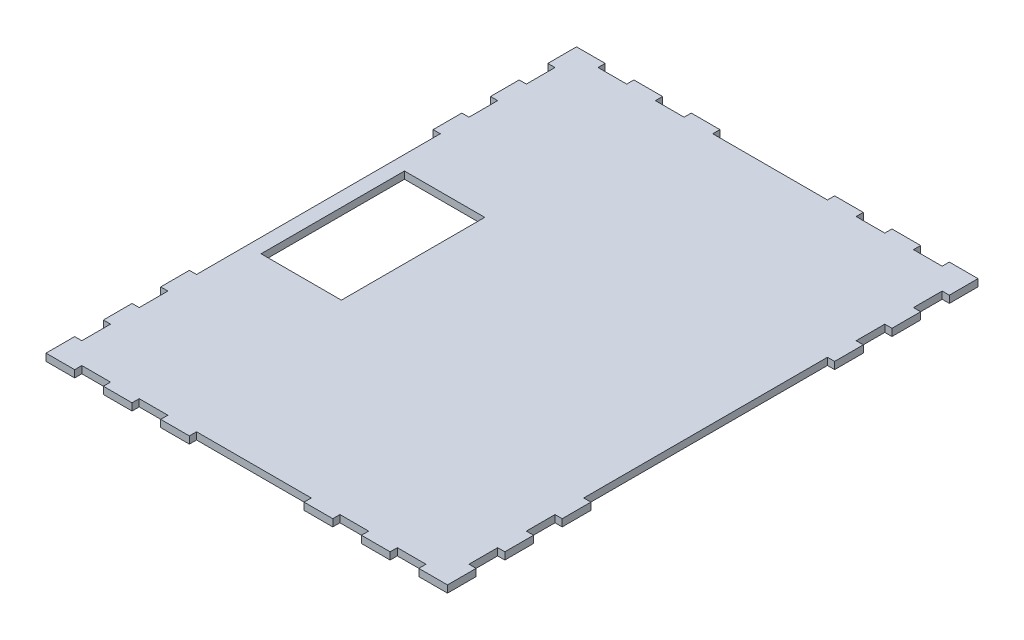
SolidWorks part; units mm, degrees
material "Acrylic (Medium-high impact)"
ref_plane "Front Plane" through (0, 0, 0) normal (0, 0, 1) x (1, 0, 0)
ref_plane "Top Plane" through (0, 0, 0) normal (0, 1, 0) x (1, 0, 0)
ref_plane "Right Plane" through (0, 0, 0) normal (1, 0, 0) x (0, 0, -1)
sketch "Sketch1" plane through (0, 0, 0) normal (0, 1, 0) x (1, 0, 0)
  line L0 (0, 209.55) -> (0, 196.85)
  line L1 (0, 0) -> (177.8, 0)
  line L2 (0, 0) -> (0, 234.95)
  line L3 (0, 234.95) -> (177.8, 234.95)
  line L4 (177.8, 0) -> (177.8, 234.95)
  line L5 (0, 234.95) -> (3.175, 234.95)
  line L6 (0, 234.95) -> (0, 0)
  line L7 (0, 0) -> (3.175, 0)
  line L8 (3.175, 234.95) -> (3.175, 0)
  line L9 (177.8, 234.95) -> (174.625, 234.95)
  line L10 (177.8, 234.95) -> (177.8, 0)
  line L11 (177.8, 0) -> (174.625, 0)
  line L12 (174.625, 234.95) -> (174.625, 0)
  line L13 (0, 234.95) -> (3.175, 234.95)
  line L14 (0, 234.95) -> (0, 222.25)
  line L15 (0, 222.25) -> (3.175, 222.25)
  line L16 (3.175, 234.95) -> (3.175, 222.25)
  line L17 (0, 209.55) -> (3.175, 209.55)
  line L18 (3.175, 209.55) -> (3.175, 196.85)
  line L19 (0, 196.85) -> (3.175, 196.85)
  line L20 (0, 184.15) -> (0, 171.45)
  line L21 (0, 184.15) -> (3.175, 184.15)
  line L22 (3.175, 184.15) -> (3.175, 171.45)
  line L23 (0, 171.45) -> (3.175, 171.45)
  line L24 (0, 117.475) -> (177.8, 117.475) construction
  line L25 (88.9, 234.95) -> (88.9, 0) construction
  line L26 (177.8, 171.45) -> (174.625, 171.45)
  line L27 (174.625, 184.15) -> (174.625, 171.45)
  line L28 (177.8, 184.15) -> (174.625, 184.15)
  line L29 (177.8, 184.15) -> (177.8, 171.45)
  line L30 (177.8, 196.85) -> (174.625, 196.85)
  line L31 (174.625, 209.55) -> (174.625, 196.85)
  line L32 (177.8, 209.55) -> (174.625, 209.55)
  line L33 (174.625, 234.95) -> (174.625, 222.25)
  line L34 (177.8, 222.25) -> (174.625, 222.25)
  line L35 (177.8, 234.95) -> (177.8, 222.25)
  line L36 (177.8, 234.95) -> (174.625, 234.95)
  line L37 (177.8, 234.95) -> (177.8, 0)
  line L38 (177.8, 234.95) -> (174.625, 234.95)
  line L39 (177.8, 209.55) -> (177.8, 196.85)
  line L40 (177.8, 25.4) -> (177.8, 38.1)
  line L41 (177.8, 0) -> (174.625, 0)
  line L42 (177.8, 0) -> (174.625, 0)
  line L43 (177.8, 0) -> (177.8, 12.7)
  line L44 (177.8, 12.7) -> (174.625, 12.7)
  line L45 (174.625, 0) -> (174.625, 12.7)
  line L46 (177.8, 25.4) -> (174.625, 25.4)
  line L47 (174.625, 25.4) -> (174.625, 38.1)
  line L48 (177.8, 38.1) -> (174.625, 38.1)
  line L49 (177.8, 50.8) -> (177.8, 63.5)
  line L50 (177.8, 50.8) -> (174.625, 50.8)
  line L51 (174.625, 50.8) -> (174.625, 63.5)
  line L52 (177.8, 63.5) -> (174.625, 63.5)
  line L53 (0, 63.5) -> (3.175, 63.5)
  line L54 (3.175, 50.8) -> (3.175, 63.5)
  line L55 (0, 50.8) -> (3.175, 50.8)
  line L56 (0, 50.8) -> (0, 63.5)
  line L57 (0, 38.1) -> (3.175, 38.1)
  line L58 (3.175, 25.4) -> (3.175, 38.1)
  line L59 (0, 25.4) -> (3.175, 25.4)
  line L60 (3.175, 0) -> (3.175, 12.7)
  line L61 (0, 12.7) -> (3.175, 12.7)
  line L62 (0, 0) -> (0, 12.7)
  line L63 (0, 0) -> (3.175, 0)
  line L64 (177.8, 0) -> (174.625, 0)
  line L65 (0, 0) -> (3.175, 0)
  line L66 (0, 0) -> (177.8, 0)
  line L67 (0, 25.4) -> (0, 38.1)
  dimension "D1" = 234.95
  dimension "D2" = 177.8
  dimension "D3" = 3.175
  dimension "D4" = 3.175
  dimension "D5" = 12.7
  dimension "D6" = 3.175
  dimension "D7" = 3
extrude "Boss-Extrude1" add sketch "Sketch1" along normal blind 3.175 contours L6 L55 L8 L53 | L6 L59 L8 L57 | L61 L2 L1 L8 | L6 L23 L8 L21 | L0 L19 L8 L17 | L6 L15 L8 L3 | L4 L44 L12 L1 | L37 L48 L12 L46 | L37 L52 L12 L50 | L34 L10 L3 L12 | L10 L32 L12 L30 | L10 L28 L12 L26 | L52 L12 L26 L27 L28 L30 L31 L32 L34 L33 L3 L8 L1 L45 L44 L46 L47 L48 L50 L51 region at (1.5875, 0, -203.2) region at (1.5875, 0, -228.6) region at (88.9, 0, -117.475) region at (1.5875, 0, -177.8) region at (1.5875, 0, -57.15) region at (176.2125, 0, -228.6) region at (1.5875, 0, -31.75) region at (176.2125, 0, -203.2) region at (1.5875, 0, -6.35) region at (176.2125, 0, -177.8) region at (176.2125, 0, -57.15) region at (176.2125, 0, -6.35) region at (176.2125, 0, -31.75)
sketch "Sketch5" plane through (0, 3.175, 0) normal (0, 1, 0) x (1, 0, 0)
  line L0 (88.9, 0) -> (88.9, 18.3402) construction
  line L1 (0, 0) -> (177.8, 0) construction
  line L3 (0, 0) -> (12.7, 0)
  line L4 (0, 0) -> (0, 3.175)
  line L5 (0, 3.175) -> (12.7, 3.175)
  line L6 (12.7, 0) -> (12.7, 3.175)
  line L10 (25.4, 3.175) -> (38.1, 3.175)
  line L11 (25.4, 0) -> (38.1, 0)
  line L12 (38.1, 0) -> (38.1, 3.175)
  line L13 (25.4, 0) -> (25.4, 3.175)
  line L14 (50.8, 3.175) -> (63.5, 3.175)
  line L15 (50.8, 0) -> (63.5, 0)
  line L16 (63.5, 0) -> (63.5, 3.175)
  line L17 (50.8, 0) -> (50.8, 3.175)
  line L18 (0, 3.175) -> (177.8, 3.175)
  line L19 (127, 0) -> (127, 3.175)
  line L20 (114.3, 0) -> (114.3, 3.175)
  line L21 (127, 0) -> (114.3, 0)
  line L22 (127, 3.175) -> (114.3, 3.175)
  line L23 (152.4, 0) -> (152.4, 3.175)
  line L24 (139.7, 0) -> (139.7, 3.175)
  line L25 (152.4, 0) -> (139.7, 0)
  line L26 (152.4, 3.175) -> (139.7, 3.175)
  line L27 (165.1, 0) -> (165.1, 3.175)
  line L28 (177.8, 3.175) -> (165.1, 3.175)
  line L29 (177.8, 0) -> (177.8, 3.175)
  line L30 (177.8, 0) -> (165.1, 0)
  line L63 (0, 63.5) -> (0, 50.8)
  line L64 (0, 50.8) -> (3.175, 50.8)
  line L65 (3.175, 50.8) -> (3.175, 38.1)
  line L66 (3.175, 38.1) -> (0, 38.1)
  line L67 (0, 38.1) -> (0, 25.4)
  line L68 (0, 25.4) -> (3.175, 25.4)
  line L69 (3.175, 25.4) -> (3.175, 12.7)
  line L70 (3.175, 12.7) -> (0, 12.7)
  line L71 (0, 12.7) -> (0, 0)
  line L72 (0, 0) -> (177.8, 0)
  line L73 (177.8, 0) -> (177.8, 12.7)
  line L74 (177.8, 12.7) -> (174.625, 12.7)
  line L75 (174.625, 12.7) -> (174.625, 25.4)
  line L76 (174.625, 25.4) -> (177.8, 25.4)
  line L77 (177.8, 25.4) -> (177.8, 38.1)
  line L78 (177.8, 38.1) -> (174.625, 38.1)
  line L79 (174.625, 38.1) -> (174.625, 50.8)
  line L80 (174.625, 50.8) -> (177.8, 50.8)
  line L81 (177.8, 50.8) -> (177.8, 63.5)
  line L82 (177.8, 63.5) -> (174.625, 63.5)
  line L83 (174.625, 63.5) -> (174.625, 171.45)
  line L84 (174.625, 171.45) -> (177.8, 171.45)
  line L85 (177.8, 171.45) -> (177.8, 184.15)
  line L86 (177.8, 184.15) -> (174.625, 184.15)
  line L87 (174.625, 184.15) -> (174.625, 196.85)
  line L88 (174.625, 196.85) -> (177.8, 196.85)
  line L89 (177.8, 196.85) -> (177.8, 209.55)
  line L90 (177.8, 209.55) -> (174.625, 209.55)
  line L91 (174.625, 209.55) -> (174.625, 222.25)
  line L92 (174.625, 222.25) -> (177.8, 222.25)
  line L93 (177.8, 222.25) -> (177.8, 234.95)
  line L94 (177.8, 234.95) -> (0, 234.95)
  line L95 (0, 234.95) -> (0, 222.25)
  line L96 (0, 222.25) -> (3.175, 222.25)
  line L97 (3.175, 222.25) -> (3.175, 209.55)
  line L98 (3.175, 209.55) -> (0, 209.55)
  line L99 (0, 209.55) -> (0, 196.85)
  line L100 (0, 196.85) -> (3.175, 196.85)
  line L101 (3.175, 196.85) -> (3.175, 184.15)
  line L102 (3.175, 184.15) -> (0, 184.15)
  line L103 (0, 184.15) -> (0, 171.45)
  line L104 (0, 171.45) -> (3.175, 171.45)
  line L105 (3.175, 171.45) -> (3.175, 63.5)
  line L106 (3.175, 63.5) -> (0, 63.5)
  line L107 (0, 63.5) -> (0, 50.8)
  line L108 (0, 50.8) -> (3.175, 50.8)
  line L109 (3.175, 50.8) -> (3.175, 38.1)
  line L110 (3.175, 38.1) -> (0, 38.1)
  line L111 (0, 38.1) -> (0, 25.4)
  line L112 (0, 25.4) -> (3.175, 25.4)
  line L113 (3.175, 25.4) -> (3.175, 12.7)
  line L114 (3.175, 12.7) -> (0, 12.7)
  line L115 (0, 12.7) -> (0, 0)
  line L116 (0, 0) -> (177.8, 0)
  line L117 (177.8, 0) -> (177.8, 12.7)
  line L118 (177.8, 12.7) -> (174.625, 12.7)
  line L119 (174.625, 12.7) -> (174.625, 25.4)
  line L120 (174.625, 25.4) -> (177.8, 25.4)
  line L121 (177.8, 25.4) -> (177.8, 38.1)
  line L122 (177.8, 38.1) -> (174.625, 38.1)
  line L123 (174.625, 38.1) -> (174.625, 50.8)
  line L124 (174.625, 50.8) -> (177.8, 50.8)
  line L125 (177.8, 50.8) -> (177.8, 63.5)
  line L126 (177.8, 63.5) -> (174.625, 63.5)
  line L127 (174.625, 63.5) -> (174.625, 171.45)
  line L128 (174.625, 171.45) -> (177.8, 171.45)
  line L129 (177.8, 171.45) -> (177.8, 184.15)
  line L130 (177.8, 184.15) -> (174.625, 184.15)
  line L131 (174.625, 184.15) -> (174.625, 196.85)
  line L132 (174.625, 196.85) -> (177.8, 196.85)
  line L133 (177.8, 196.85) -> (177.8, 209.55)
  line L134 (177.8, 209.55) -> (174.625, 209.55)
  line L135 (174.625, 209.55) -> (174.625, 222.25)
  line L136 (174.625, 222.25) -> (177.8, 222.25)
  line L137 (177.8, 222.25) -> (177.8, 234.95)
  line L138 (177.8, 234.95) -> (0, 234.95)
  line L139 (0, 234.95) -> (0, 222.25)
  line L140 (0, 222.25) -> (3.175, 222.25)
  line L141 (3.175, 222.25) -> (3.175, 209.55)
  line L142 (3.175, 209.55) -> (0, 209.55)
  line L143 (0, 209.55) -> (0, 196.85)
  line L144 (0, 196.85) -> (3.175, 196.85)
  line L145 (3.175, 196.85) -> (3.175, 184.15)
  line L146 (3.175, 184.15) -> (0, 184.15)
  line L147 (0, 184.15) -> (0, 171.45)
  line L148 (0, 171.45) -> (3.175, 171.45)
  line L149 (3.175, 171.45) -> (3.175, 63.5)
  line L150 (3.175, 63.5) -> (0, 63.5)
  point P22 (88.9, 3.175)
  dimension "D1" = 3.175
  dimension "D2" = 12.7
  dimension "D4" = 0
  dimension "D3" = 3
extrude "Cut-Extrude4" cut sketch "Sketch5" against normal blind 7.62 contours L6 L116 L13 L18 | L12 L116 L17 L18 | L116 L0 L18 L16 | L0 L116 L20 L18 | L19 L116 L24 L18 | L23 L116 L27 L18 region at (76.2, 3.175, -1.5875) region at (101.6, 3.175, -1.5875) region at (44.45, 3.175, -1.5875) region at (133.35, 3.175, -1.5875) region at (19.05, 3.175, -1.5875) region at (158.75, 3.175, -1.5875)
ref_plane "Plane2" through (0, 0, -117.475) normal (0, 0, 1) x (1, 0, 0)
mirror "Mirror1" about plane through (0, 0, -117.475) normal (0, 0, 1) of "Cut-Extrude4"
sketch "Sketch7" plane through (0, 3.175, 0) normal (0, 1, 0) x (1, 0, 0)
  line L0 (3.175, 117.475) -> (174.625, 117.475) construction
  line L1 (3.175, 171.45) -> (3.175, 63.5) construction
  line L2 (174.625, 171.45) -> (174.625, 63.5) construction
  line L3 (3.175, 117.475) -> (9.525, 117.475) construction
  line L4 (9.525, 117.475) -> (9.525, 149.225)
  line L6 (9.525, 149.225) -> (45.085, 149.225)
  line L7 (9.525, 149.225) -> (9.525, 85.725)
  line L8 (9.525, 85.725) -> (45.085, 85.725)
  line L9 (45.085, 149.225) -> (45.085, 85.725)
  dimension "D1" = 6.35
  dimension "D2" = 31.75
  dimension "D3" = 63.5
  dimension "D4" = 35.56
extrude "Cut-Extrude5" cut sketch "Sketch7" against normal blind 7.62 contours L6 L9 L8 L7
